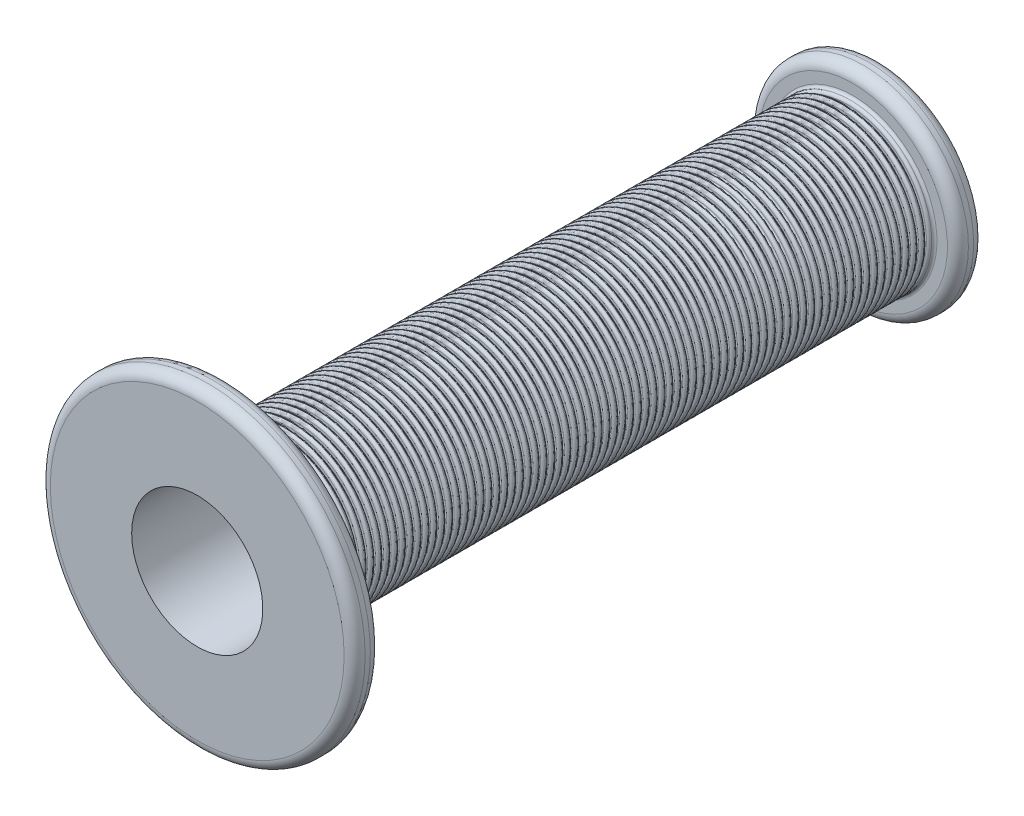
SolidWorks part; units mm, degrees
ref_plane "Front Plane" through (0, 0, 0) normal (0, 0, 1) x (1, 0, 0)
ref_plane "Top Plane" through (0, 0, 0) normal (0, 1, 0) x (1, 0, 0)
ref_plane "Right Plane" through (0, 0, 0) normal (1, 0, 0) x (0, 0, -1)
sketch "Sketch1" plane through (0, 0, 0) normal (0, 0, 1) x (1, 0, 0)
  circle A0 centre (0, 0) radius 15.5
  dimension "D1" = 31
extrude "Boss-Extrude1" add sketch "Sketch1" along normal blind 130
sketch "Sketch3" plane through (0, 0, 130) normal (0, 0, 1) x (1, 0, 0)
  circle A0 centre (0, 0) radius 30
  dimension "D1" = 60
extrude "Boss-Extrude2" add sketch "Sketch3" against normal blind 5
sketch "Sketch4" plane through (0, 0, 0) normal (0, 0, -1) x (-1, 0, 0)
  circle A0 centre (0, 0) radius 20
  dimension "D1" = 40
extrude "Boss-Extrude3" add sketch "Sketch4" against normal blind 5
fillet "Fillet1" radius 2 4 edges at (-20, 0, 0) (-20, 0, 5) (30, 0, 130) (30, 0, 125)
fillet "Fillet2" radius 5 1 edges at (15.5, 0, 125)
sketch "Sketch5" plane through (0, 0, 0) normal (1, 0, 0) x (0, 0, -1)
  line L0 (-5, 15.5) -> (-120, 15.5) construction
  line L1 (-6, 20.2474) -> (-6.5, 20.2474)
  line L2 (-6, 20.2474) -> (-6, 14.5)
  line L3 (-6, 14.5) -> (-6.5, 14.5)
  line L4 (-6.5, 20.2474) -> (-6.5, 14.5)
  line L5 (-5, 15.5) -> (-5, -15.5) construction
  line L6 (-7.5, 20.2474) -> (-7.5, 14.5)
  line L7 (-7.5, 20.2474) -> (-8, 20.2474)
  line L8 (-8, 20.2474) -> (-8, 14.5)
  line L9 (-7.5, 14.5) -> (-8, 14.5)
  line L10 (-9, 20.2474) -> (-9, 14.5)
  line L11 (-9, 20.2474) -> (-9.5, 20.2474)
  line L12 (-9.5, 20.2474) -> (-9.5, 14.5)
  line L13 (-9, 14.5) -> (-9.5, 14.5)
  line L14 (-10.5, 20.2474) -> (-10.5, 14.5)
  line L15 (-10.5, 20.2474) -> (-11, 20.2474)
  line L16 (-11, 20.2474) -> (-11, 14.5)
  line L17 (-10.5, 14.5) -> (-11, 14.5)
  line L18 (-12, 20.2474) -> (-12, 14.5)
  line L19 (-12, 20.2474) -> (-12.5, 20.2474)
  line L20 (-12.5, 20.2474) -> (-12.5, 14.5)
  line L21 (-12, 14.5) -> (-12.5, 14.5)
  line L22 (-13.5, 20.2474) -> (-13.5, 14.5)
  line L23 (-13.5, 20.2474) -> (-14, 20.2474)
  line L24 (-14, 20.2474) -> (-14, 14.5)
  line L25 (-13.5, 14.5) -> (-14, 14.5)
  line L26 (-15, 20.2474) -> (-15, 14.5)
  line L27 (-15, 20.2474) -> (-15.5, 20.2474)
  line L28 (-15.5, 20.2474) -> (-15.5, 14.5)
  line L29 (-15, 14.5) -> (-15.5, 14.5)
  line L30 (-16.5, 20.2474) -> (-16.5, 14.5)
  line L31 (-16.5, 20.2474) -> (-17, 20.2474)
  line L32 (-17, 20.2474) -> (-17, 14.5)
  line L33 (-16.5, 14.5) -> (-17, 14.5)
  line L34 (-18, 20.2474) -> (-18, 14.5)
  line L35 (-18, 20.2474) -> (-18.5, 20.2474)
  line L36 (-18.5, 20.2474) -> (-18.5, 14.5)
  line L37 (-18, 14.5) -> (-18.5, 14.5)
  line L38 (-19.5, 20.2474) -> (-19.5, 14.5)
  line L39 (-19.5, 20.2474) -> (-20, 20.2474)
  line L40 (-20, 20.2474) -> (-20, 14.5)
  line L41 (-19.5, 14.5) -> (-20, 14.5)
  line L42 (-21, 20.2474) -> (-21, 14.5)
  line L43 (-21, 20.2474) -> (-21.5, 20.2474)
  line L44 (-21.5, 20.2474) -> (-21.5, 14.5)
  line L45 (-21, 14.5) -> (-21.5, 14.5)
  line L46 (-22.5, 20.2474) -> (-22.5, 14.5)
  line L47 (-22.5, 20.2474) -> (-23, 20.2474)
  line L48 (-23, 20.2474) -> (-23, 14.5)
  line L49 (-22.5, 14.5) -> (-23, 14.5)
  line L50 (-24, 20.2474) -> (-24, 14.5)
  line L51 (-24, 20.2474) -> (-24.5, 20.2474)
  line L52 (-24.5, 20.2474) -> (-24.5, 14.5)
  line L53 (-24, 14.5) -> (-24.5, 14.5)
  line L54 (-25.5, 20.2474) -> (-25.5, 14.5)
  line L55 (-25.5, 20.2474) -> (-26, 20.2474)
  line L56 (-26, 20.2474) -> (-26, 14.5)
  line L57 (-25.5, 14.5) -> (-26, 14.5)
  line L58 (-27, 20.2474) -> (-27, 14.5)
  line L59 (-27, 20.2474) -> (-27.5, 20.2474)
  line L60 (-27.5, 20.2474) -> (-27.5, 14.5)
  line L61 (-27, 14.5) -> (-27.5, 14.5)
  line L62 (-28.5, 20.2474) -> (-28.5, 14.5)
  line L63 (-28.5, 20.2474) -> (-29, 20.2474)
  line L64 (-29, 20.2474) -> (-29, 14.5)
  line L65 (-28.5, 14.5) -> (-29, 14.5)
  line L66 (-30, 20.2474) -> (-30, 14.5)
  line L67 (-30, 20.2474) -> (-30.5, 20.2474)
  line L68 (-30.5, 20.2474) -> (-30.5, 14.5)
  line L69 (-30, 14.5) -> (-30.5, 14.5)
  line L70 (-31.5, 20.2474) -> (-31.5, 14.5)
  line L71 (-31.5, 20.2474) -> (-32, 20.2474)
  line L72 (-32, 20.2474) -> (-32, 14.5)
  line L73 (-31.5, 14.5) -> (-32, 14.5)
  line L74 (-33, 20.2474) -> (-33, 14.5)
  line L75 (-33, 20.2474) -> (-33.5, 20.2474)
  line L76 (-33.5, 20.2474) -> (-33.5, 14.5)
  line L77 (-33, 14.5) -> (-33.5, 14.5)
  line L78 (-34.5, 20.2474) -> (-34.5, 14.5)
  line L79 (-34.5, 20.2474) -> (-35, 20.2474)
  line L80 (-35, 20.2474) -> (-35, 14.5)
  line L81 (-34.5, 14.5) -> (-35, 14.5)
  line L82 (-36, 20.2474) -> (-36, 14.5)
  line L83 (-36, 20.2474) -> (-36.5, 20.2474)
  line L84 (-36.5, 20.2474) -> (-36.5, 14.5)
  line L85 (-36, 14.5) -> (-36.5, 14.5)
  line L86 (-37.5, 20.2474) -> (-37.5, 14.5)
  line L87 (-37.5, 20.2474) -> (-38, 20.2474)
  line L88 (-38, 20.2474) -> (-38, 14.5)
  line L89 (-37.5, 14.5) -> (-38, 14.5)
  line L90 (-39, 20.2474) -> (-39, 14.5)
  line L91 (-39, 20.2474) -> (-39.5, 20.2474)
  line L92 (-39.5, 20.2474) -> (-39.5, 14.5)
  line L93 (-39, 14.5) -> (-39.5, 14.5)
  line L94 (-40.5, 20.2474) -> (-40.5, 14.5)
  line L95 (-40.5, 20.2474) -> (-41, 20.2474)
  line L96 (-41, 20.2474) -> (-41, 14.5)
  line L97 (-40.5, 14.5) -> (-41, 14.5)
  line L98 (-42, 20.2474) -> (-42, 14.5)
  line L99 (-42, 20.2474) -> (-42.5, 20.2474)
  line L100 (-42.5, 20.2474) -> (-42.5, 14.5)
  line L101 (-42, 14.5) -> (-42.5, 14.5)
  line L102 (-43.5, 20.2474) -> (-43.5, 14.5)
  line L103 (-43.5, 20.2474) -> (-44, 20.2474)
  line L104 (-44, 20.2474) -> (-44, 14.5)
  line L105 (-43.5, 14.5) -> (-44, 14.5)
  line L106 (-45, 20.2474) -> (-45, 14.5)
  line L107 (-45, 20.2474) -> (-45.5, 20.2474)
  line L108 (-45.5, 20.2474) -> (-45.5, 14.5)
  line L109 (-45, 14.5) -> (-45.5, 14.5)
  line L110 (-46.5, 20.2474) -> (-46.5, 14.5)
  line L111 (-46.5, 20.2474) -> (-47, 20.2474)
  line L112 (-47, 20.2474) -> (-47, 14.5)
  line L113 (-46.5, 14.5) -> (-47, 14.5)
  line L114 (-48, 20.2474) -> (-48, 14.5)
  line L115 (-48, 20.2474) -> (-48.5, 20.2474)
  line L116 (-48.5, 20.2474) -> (-48.5, 14.5)
  line L117 (-48, 14.5) -> (-48.5, 14.5)
  line L118 (-49.5, 20.2474) -> (-49.5, 14.5)
  line L119 (-49.5, 20.2474) -> (-50, 20.2474)
  line L120 (-50, 20.2474) -> (-50, 14.5)
  line L121 (-49.5, 14.5) -> (-50, 14.5)
  line L122 (-51, 20.2474) -> (-51, 14.5)
  line L123 (-51, 20.2474) -> (-51.5, 20.2474)
  line L124 (-51.5, 20.2474) -> (-51.5, 14.5)
  line L125 (-51, 14.5) -> (-51.5, 14.5)
  line L126 (-52.5, 20.2474) -> (-52.5, 14.5)
  line L127 (-52.5, 20.2474) -> (-53, 20.2474)
  line L128 (-53, 20.2474) -> (-53, 14.5)
  line L129 (-52.5, 14.5) -> (-53, 14.5)
  line L130 (-54, 20.2474) -> (-54, 14.5)
  line L131 (-54, 20.2474) -> (-54.5, 20.2474)
  line L132 (-54.5, 20.2474) -> (-54.5, 14.5)
  line L133 (-54, 14.5) -> (-54.5, 14.5)
  line L134 (-55.5, 20.2474) -> (-55.5, 14.5)
  line L135 (-55.5, 20.2474) -> (-56, 20.2474)
  line L136 (-56, 20.2474) -> (-56, 14.5)
  line L137 (-55.5, 14.5) -> (-56, 14.5)
  line L138 (-57, 20.2474) -> (-57, 14.5)
  line L139 (-57, 20.2474) -> (-57.5, 20.2474)
  line L140 (-57.5, 20.2474) -> (-57.5, 14.5)
  line L141 (-57, 14.5) -> (-57.5, 14.5)
  line L142 (-58.5, 20.2474) -> (-58.5, 14.5)
  line L143 (-58.5, 20.2474) -> (-59, 20.2474)
  line L144 (-59, 20.2474) -> (-59, 14.5)
  line L145 (-58.5, 14.5) -> (-59, 14.5)
  line L146 (-60, 20.2474) -> (-60, 14.5)
  line L147 (-60, 20.2474) -> (-60.5, 20.2474)
  line L148 (-60.5, 20.2474) -> (-60.5, 14.5)
  line L149 (-60, 14.5) -> (-60.5, 14.5)
  line L150 (-61.5, 20.2474) -> (-61.5, 14.5)
  line L151 (-61.5, 20.2474) -> (-62, 20.2474)
  line L152 (-62, 20.2474) -> (-62, 14.5)
  line L153 (-61.5, 14.5) -> (-62, 14.5)
  line L154 (-63, 20.2474) -> (-63, 14.5)
  line L155 (-63, 20.2474) -> (-63.5, 20.2474)
  line L156 (-63.5, 20.2474) -> (-63.5, 14.5)
  line L157 (-63, 14.5) -> (-63.5, 14.5)
  line L158 (-64.5, 20.2474) -> (-64.5, 14.5)
  line L159 (-64.5, 20.2474) -> (-65, 20.2474)
  line L160 (-65, 20.2474) -> (-65, 14.5)
  line L161 (-64.5, 14.5) -> (-65, 14.5)
  line L162 (-66, 20.2474) -> (-66, 14.5)
  line L163 (-66, 20.2474) -> (-66.5, 20.2474)
  line L164 (-66.5, 20.2474) -> (-66.5, 14.5)
  line L165 (-66, 14.5) -> (-66.5, 14.5)
  line L166 (-67.5, 20.2474) -> (-67.5, 14.5)
  line L167 (-67.5, 20.2474) -> (-68, 20.2474)
  line L168 (-68, 20.2474) -> (-68, 14.5)
  line L169 (-67.5, 14.5) -> (-68, 14.5)
  line L170 (-69, 20.2474) -> (-69, 14.5)
  line L171 (-69, 20.2474) -> (-69.5, 20.2474)
  line L172 (-69.5, 20.2474) -> (-69.5, 14.5)
  line L173 (-69, 14.5) -> (-69.5, 14.5)
  line L174 (-70.5, 20.2474) -> (-70.5, 14.5)
  line L175 (-70.5, 20.2474) -> (-71, 20.2474)
  line L176 (-71, 20.2474) -> (-71, 14.5)
  line L177 (-70.5, 14.5) -> (-71, 14.5)
  line L178 (-72, 20.2474) -> (-72, 14.5)
  line L179 (-72, 20.2474) -> (-72.5, 20.2474)
  line L180 (-72.5, 20.2474) -> (-72.5, 14.5)
  line L181 (-72, 14.5) -> (-72.5, 14.5)
  line L182 (-73.5, 20.2474) -> (-73.5, 14.5)
  line L183 (-73.5, 20.2474) -> (-74, 20.2474)
  line L184 (-74, 20.2474) -> (-74, 14.5)
  line L185 (-73.5, 14.5) -> (-74, 14.5)
  line L186 (-75, 20.2474) -> (-75, 14.5)
  line L187 (-75, 20.2474) -> (-75.5, 20.2474)
  line L188 (-75.5, 20.2474) -> (-75.5, 14.5)
  line L189 (-75, 14.5) -> (-75.5, 14.5)
  line L190 (-76.5, 20.2474) -> (-76.5, 14.5)
  line L191 (-76.5, 20.2474) -> (-77, 20.2474)
  line L192 (-77, 20.2474) -> (-77, 14.5)
  line L193 (-76.5, 14.5) -> (-77, 14.5)
  line L194 (-78, 20.2474) -> (-78, 14.5)
  line L195 (-78, 20.2474) -> (-78.5, 20.2474)
  line L196 (-78.5, 20.2474) -> (-78.5, 14.5)
  line L197 (-78, 14.5) -> (-78.5, 14.5)
  line L198 (-79.5, 20.2474) -> (-79.5, 14.5)
  line L199 (-79.5, 20.2474) -> (-80, 20.2474)
  line L200 (-80, 20.2474) -> (-80, 14.5)
  line L201 (-79.5, 14.5) -> (-80, 14.5)
  line L202 (-81, 20.2474) -> (-81, 14.5)
  line L203 (-81, 20.2474) -> (-81.5, 20.2474)
  line L204 (-81.5, 20.2474) -> (-81.5, 14.5)
  line L205 (-81, 14.5) -> (-81.5, 14.5)
  line L206 (-82.5, 20.2474) -> (-82.5, 14.5)
  line L207 (-82.5, 20.2474) -> (-83, 20.2474)
  line L208 (-83, 20.2474) -> (-83, 14.5)
  line L209 (-82.5, 14.5) -> (-83, 14.5)
  line L210 (-84, 20.2474) -> (-84, 14.5)
  line L211 (-84, 20.2474) -> (-84.5, 20.2474)
  line L212 (-84.5, 20.2474) -> (-84.5, 14.5)
  line L213 (-84, 14.5) -> (-84.5, 14.5)
  line L214 (-85.5, 20.2474) -> (-85.5, 14.5)
  line L215 (-85.5, 20.2474) -> (-86, 20.2474)
  line L216 (-86, 20.2474) -> (-86, 14.5)
  line L217 (-85.5, 14.5) -> (-86, 14.5)
  line L218 (-87, 20.2474) -> (-87, 14.5)
  line L219 (-87, 20.2474) -> (-87.5, 20.2474)
  line L220 (-87.5, 20.2474) -> (-87.5, 14.5)
  line L221 (-87, 14.5) -> (-87.5, 14.5)
  line L222 (-88.5, 20.2474) -> (-88.5, 14.5)
  line L223 (-88.5, 20.2474) -> (-89, 20.2474)
  line L224 (-89, 20.2474) -> (-89, 14.5)
  line L225 (-88.5, 14.5) -> (-89, 14.5)
  line L226 (-90, 20.2474) -> (-90, 14.5)
  line L227 (-90, 20.2474) -> (-90.5, 20.2474)
  line L228 (-90.5, 20.2474) -> (-90.5, 14.5)
  line L229 (-90, 14.5) -> (-90.5, 14.5)
  line L230 (-91.5, 20.2474) -> (-91.5, 14.5)
  line L231 (-91.5, 20.2474) -> (-92, 20.2474)
  line L232 (-92, 20.2474) -> (-92, 14.5)
  line L233 (-91.5, 14.5) -> (-92, 14.5)
  line L234 (-93, 20.2474) -> (-93, 14.5)
  line L235 (-93, 20.2474) -> (-93.5, 20.2474)
  line L236 (-93.5, 20.2474) -> (-93.5, 14.5)
  line L237 (-93, 14.5) -> (-93.5, 14.5)
  line L238 (-94.5, 20.2474) -> (-94.5, 14.5)
  line L239 (-94.5, 20.2474) -> (-95, 20.2474)
  line L240 (-95, 20.2474) -> (-95, 14.5)
  line L241 (-94.5, 14.5) -> (-95, 14.5)
  line L242 (-96, 20.2474) -> (-96, 14.5)
  line L243 (-96, 20.2474) -> (-96.5, 20.2474)
  line L244 (-96.5, 20.2474) -> (-96.5, 14.5)
  line L245 (-96, 14.5) -> (-96.5, 14.5)
  line L246 (-97.5, 20.2474) -> (-97.5, 14.5)
  line L247 (-97.5, 20.2474) -> (-98, 20.2474)
  line L248 (-98, 20.2474) -> (-98, 14.5)
  line L249 (-97.5, 14.5) -> (-98, 14.5)
  line L250 (-99, 20.2474) -> (-99, 14.5)
  line L251 (-99, 20.2474) -> (-99.5, 20.2474)
  line L252 (-99.5, 20.2474) -> (-99.5, 14.5)
  line L253 (-99, 14.5) -> (-99.5, 14.5)
  line L254 (-100.5, 20.2474) -> (-100.5, 14.5)
  line L255 (-100.5, 20.2474) -> (-101, 20.2474)
  line L256 (-101, 20.2474) -> (-101, 14.5)
  line L257 (-100.5, 14.5) -> (-101, 14.5)
  line L258 (-102, 20.2474) -> (-102, 14.5)
  line L259 (-102, 20.2474) -> (-102.5, 20.2474)
  line L260 (-102.5, 20.2474) -> (-102.5, 14.5)
  line L261 (-102, 14.5) -> (-102.5, 14.5)
  line L262 (-103.5, 20.2474) -> (-103.5, 14.5)
  line L263 (-103.5, 20.2474) -> (-104, 20.2474)
  line L264 (-104, 20.2474) -> (-104, 14.5)
  line L265 (-103.5, 14.5) -> (-104, 14.5)
  line L266 (-105, 20.2474) -> (-105, 14.5)
  line L267 (-105, 20.2474) -> (-105.5, 20.2474)
  line L268 (-105.5, 20.2474) -> (-105.5, 14.5)
  line L269 (-105, 14.5) -> (-105.5, 14.5)
  line L270 (-106.5, 20.2474) -> (-106.5, 14.5)
  line L271 (-106.5, 20.2474) -> (-107, 20.2474)
  line L272 (-107, 20.2474) -> (-107, 14.5)
  line L273 (-106.5, 14.5) -> (-107, 14.5)
  line L274 (-108, 20.2474) -> (-108, 14.5)
  line L275 (-108, 20.2474) -> (-108.5, 20.2474)
  line L276 (-108.5, 20.2474) -> (-108.5, 14.5)
  line L277 (-108, 14.5) -> (-108.5, 14.5)
  line L278 (-109.5, 20.2474) -> (-109.5, 14.5)
  line L279 (-109.5, 20.2474) -> (-110, 20.2474)
  line L280 (-110, 20.2474) -> (-110, 14.5)
  line L281 (-109.5, 14.5) -> (-110, 14.5)
  line L282 (-111, 20.2474) -> (-111, 14.5)
  line L283 (-111, 20.2474) -> (-111.5, 20.2474)
  line L284 (-111.5, 20.2474) -> (-111.5, 14.5)
  line L285 (-111, 14.5) -> (-111.5, 14.5)
  line L286 (-112.5, 20.2474) -> (-112.5, 14.5)
  line L287 (-112.5, 20.2474) -> (-113, 20.2474)
  line L288 (-113, 20.2474) -> (-113, 14.5)
  line L289 (-112.5, 14.5) -> (-113, 14.5)
  line L290 (-114, 20.2474) -> (-114, 14.5)
  line L291 (-114, 20.2474) -> (-114.5, 20.2474)
  line L292 (-114.5, 20.2474) -> (-114.5, 14.5)
  line L293 (-114, 14.5) -> (-114.5, 14.5)
  line L294 (-115.5, 20.2474) -> (-115.5, 14.5)
  line L295 (-115.5, 20.2474) -> (-116, 20.2474)
  line L296 (-116, 20.2474) -> (-116, 14.5)
  line L297 (-115.5, 14.5) -> (-116, 14.5)
  line L298 (-117, 20.2474) -> (-117, 14.5)
  line L299 (-117, 20.2474) -> (-117.5, 20.2474)
  line L300 (-117.5, 20.2474) -> (-117.5, 14.5)
  line L301 (-117, 14.5) -> (-117.5, 14.5)
  line L302 (-118.5, 20.2474) -> (-118.5, 14.5)
  line L303 (-118.5, 20.2474) -> (-119, 20.2474)
  line L304 (-119, 20.2474) -> (-119, 14.5)
  line L305 (-118.5, 14.5) -> (-119, 14.5)
  line L306 (0, 0) -> (-142.4445, 0) construction
  point P4 (-6.25, 14.5)
  dimension "D1" = 0.5
  dimension "D2" = 1
  dimension "D3" = 1
  dimension "D4" = 76
revolve "Cut-Revolve1" cut sketch "Sketch5" angle 360 about L306
fillet "Fillet4" radius 0.5 39 edges at (15.5, 0, 42.5) (-15.5, 0, 72) (15.5, 0, 71) (-15.5, 0, 70.5) (15.5, 0, 69.5) (-15.5, 0, 69) (15.5, 0, 68) (-15.5, 0, 67.5) (15.5, 0, 66.5) (-15.5, 0, 66) (15.5, 0, 65) (-15.5, 0, 64.5) (15.5, 0, 63.5) (-15.5, 0, 63) (15.5, 0, 62) (-15.5, 0, 61.5) (15.5, 0, 60.5) (-15.5, 0, 60) (15.5, 0, 59) (-15.5, 0, 58.5) (15.5, 0, 57.5) (-15.5, 0, 57) (15.5, 0, 56) (-15.5, 0, 55.5) (15.5, 0, 54.5) (-15.5, 0, 54) (15.5, 0, 53) (-15.5, 0, 52.5) (15.5, 0, 51.5) (-15.5, 0, 51) (15.5, 0, 50) (-15.5, 0, 49.5) (15.5, 0, 48.5) (-15.5, 0, 48) (15.5, 0, 47) (-15.5, 0, 46.5) (15.5, 0, 45.5) (-15.5, 0, 45) (15.5, 0, 44)
fillet "Fillet5" radius 0.5 54 edges at (-15.5, 0, 31.5) (-15.5, 0, 5) (-15.5, 0, 6) (-15.5, 0, 7.5) (15.5, 0, 6.5) (-15.5, 0, 9) (15.5, 0, 8) (-15.5, 0, 10.5) (15.5, 0, 9.5) (-15.5, 0, 12) (15.5, 0, 11) (-15.5, 0, 13.5) (15.5, 0, 12.5) (-15.5, 0, 15) (15.5, 0, 14) (-15.5, 0, 16.5) (15.5, 0, 15.5) (-15.5, 0, 18) (15.5, 0, 17) (-15.5, 0, 19.5) (15.5, 0, 18.5) (-15.5, 0, 21) (15.5, 0, 20) (-15.5, 0, 22.5) (15.5, 0, 21.5) (-15.5, 0, 36) (15.5, 0, 35) (-15.5, 0, 24) (15.5, 0, 23) (-15.5, 0, 25.5) (15.5, 0, 24.5) (-15.5, 0, 27) (15.5, 0, 26) (-15.5, 0, 28.5) (15.5, 0, 27.5) (-15.5, 0, 30) (15.5, 0, 29) (-15.5, 0, 33) (15.5, 0, 32) (-15.5, 0, 34.5) (15.5, 0, 33.5) (-15.5, 0, 37.5) (15.5, 0, 36.5) (-15.5, 0, 39) (15.5, 0, 38) (-15.5, 0, 40.5) (15.5, 0, 39.5) (-15.5, 0, 43.5) (-15.5, 0, 42) (15.5, 0, 41) (-14.5, 0, 27) (-14.5, 0, 31.5) (-14.5, 0, 30) (-14.5, 0, 36)
fillet "Fillet6" radius 0.5 63 edges at (15.5, 0, 117.5) (-15.5, 0, 103.5) (15.5, 0, 102.5) (-15.5, 0, 102) (15.5, 0, 101) (-15.5, 0, 100.5) (15.5, 0, 99.5) (15.5, 0, 98) (-15.5, 0, 99) (-15.5, 0, 117) (15.5, 0, 116) (-15.5, 0, 115.5) (15.5, 0, 114.5) (-15.5, 0, 114) (15.5, 0, 113) (-15.5, 0, 112.5) (15.5, 0, 111.5) (-15.5, 0, 111) (15.5, 0, 110) (-15.5, 0, 109.5) (15.5, 0, 108.5) (-15.5, 0, 108) (15.5, 0, 107) (-15.5, 0, 106.5) (15.5, 0, 105.5) (-15.5, 0, 105) (15.5, 0, 104) (-15.5, 0, 97.5) (15.5, 0, 96.5) (-15.5, 0, 96) (15.5, 0, 95) (-15.5, 0, 94.5) (15.5, 0, 93.5) (-15.5, 0, 93) (15.5, 0, 92) (-15.5, 0, 91.5) (15.5, 0, 90.5) (-15.5, 0, 90) (15.5, 0, 89) (-15.5, 0, 88.5) (15.5, 0, 87.5) (-15.5, 0, 87) (15.5, 0, 86) (-15.5, 0, 85.5) (15.5, 0, 84.5) (-15.5, 0, 84) (15.5, 0, 83) (-15.5, 0, 82.5) (15.5, 0, 81.5) (-15.5, 0, 81) (15.5, 0, 80) (-15.5, 0, 79.5) (15.5, 0, 78.5) (-15.5, 0, 78) (15.5, 0, 77) (-15.5, 0, 76.5) (15.5, 0, 75.5) (-15.5, 0, 75) (15.5, 0, 74) (-15.5, 0, 73.5) (15.5, 0, 72.5) (15.5, 0, 119) (15.5, 0, 30.5)
sketch "Sketch6" plane through (0, 0, 0) normal (0, 0, -1) x (-1, 0, 0)
  circle A0 centre (0, 0) radius 12.5
  dimension "D1" = 25
extrude "Cut-Extrude1" cut sketch "Sketch6" against normal through all and the other way through all
